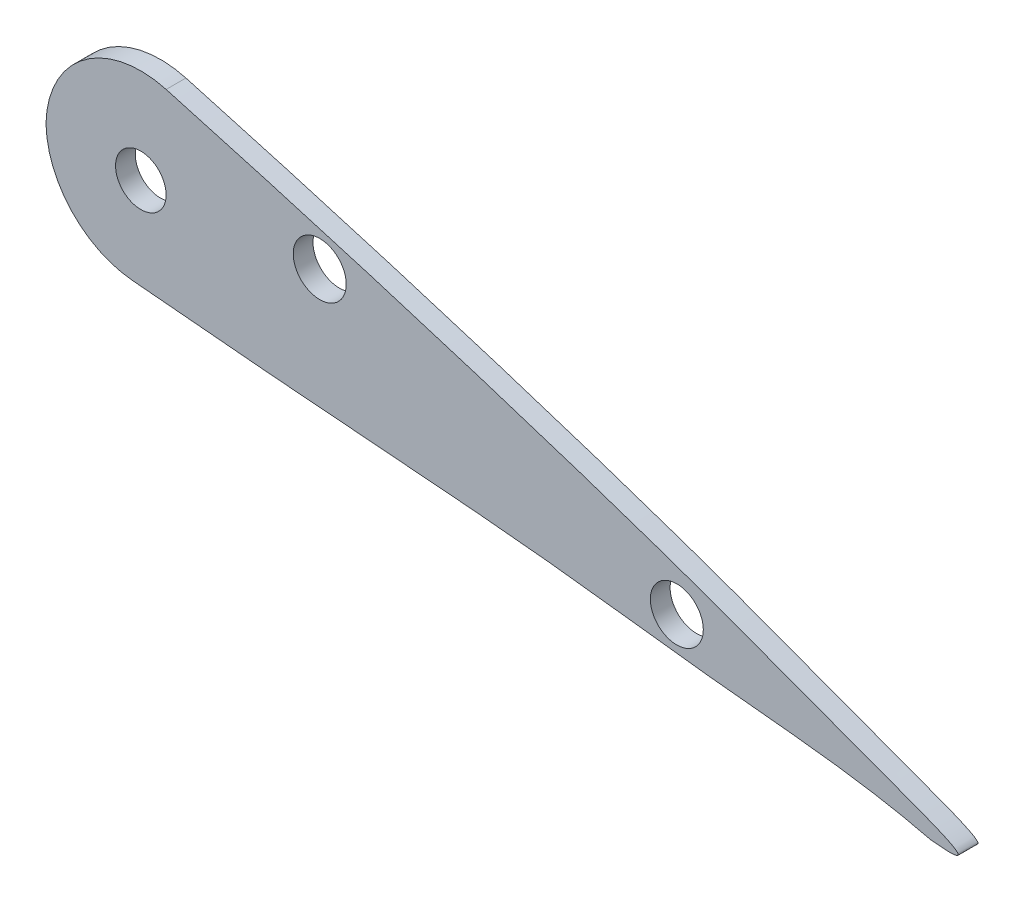
SolidWorks part; units mm, degrees
material "Balsa"
ref_plane "Front Plane" through (0, 0, 0) normal (0, 0, 1) x (1, 0, 0)
ref_plane "Top Plane" through (0, 0, 0) normal (0, 1, 0) x (1, 0, 0)
ref_plane "Right Plane" through (0, 0, 0) normal (1, 0, 0) x (0, 0, -1)
sketch "Sketch1" plane through (0, 0, 0) normal (0, 0, 1) x (1, 0, 0)
  spline S0 degree 3 poles (0.0006, 0.0001) (0.8106, 7.3592) (8.6491, 17.8566) (26.2867, 29.9752) (52.1111, 42.0692) (89.5976, 49.2908) (131.4008, 47.8848) (173.2567, 40.0411) (217.9611, 29.613) (256.9521, 19.5289) (290.3598, 8.711) (301.2732, 4.3828) (314.8169, -0.5162) (309.8463, 0.0001) knots 0 0 0 0 0.060864 0.113688 0.188609 0.312909 0.448482 0.557612 0.691544 0.852438 0.929756 0.976058 1 1 1 1
  spline S1 degree 3 poles (309.8463, 0.0001) (303.9568, 1.471) (293.9895, 2.094) (276.264, 4.5144) (260.8463, 5.4274) (235.8588, 7.8703) (205.1014, 8.8381) (157.7186, 9.0307) (110.4973, 6.1815) (66.5062, -0.5867) (36.4547, -6.0985) (15.3166, -6.1891) (1.2307, -6.9241) (0.0006, 0.0001) knots 0 0 0 0 0.057787 0.095275 0.171021 0.205339 0.335319 0.464904 0.658702 0.785512 0.893517 0.943092 1 1 1 1
extrude "Boss-Extrude1" add sketch "Sketch1" along normal blind 1.5875
sketch "Sketch2" plane through (0, 0, 1.5875) normal (0, 0, 1) x (1, 0, 0)
  circle A0 centre (20.32, 10.16) radius 6.35
  circle A1 centre (227.2963, 19.0501) radius 3.175
  dimension "D2" = 12.7
  dimension "D3" = 6.35
  dimension "D6" = 20.32
  dimension "D1" = 82.55
  dimension "D4" = 19.05
  dimension "D5" = 10.16
extrude "Cut-Extrude1" cut sketch "Sketch2" against normal through all
sketch "Sketch3" plane through (0, 0, 1.5875) normal (0, 0, 1) x (1, 0, 0)
  line L11 (-90.3395, -69.7561) -> (238.7263, -69.7561)
  line L12 (-90.3395, -69.7561) -> (-90.3395, 107.5465)
  line L13 (-90.3395, 107.5465) -> (238.7263, 107.5465)
  line L14 (238.7263, -69.7561) -> (238.7263, 107.5465)
  circle A1 centre (227.2963, 19.0501) radius 3.175 construction
  dimension "D1" = 11.43
extrude "Cut-Extrude2" cut sketch "Sketch3" against normal through all contours L14 L13 L12 L11
fillet "Fillet1" radius 7.62 2 edges at (238.7263, 7.3795, 0.7937) (238.7263, 24.1211, 0.7937)
sketch "Sketch4" plane through (0, 0, 1.5875) normal (0, 0, 1) x (1, 0, 0)
  circle A0 centre (246.3463, 14.163) radius 2.032
  dimension "D1" = 4.064
  dimension "D2" = 63.5
  dimension "D3" = 14.1628
extrude "Cut-Extrude3" cut sketch "Sketch4" against normal blind 2.54
sketch "Sketch5" plane through (0, 0, 1.5875) normal (0, 0, 1) x (1, 0, 0)
  circle A0 centre (260.7202, 15.1782) radius 2.127
  circle A1 centre (289.4099, 5.4937) radius 2.127
  point P4 (284.5248, 6.5939)
  point P5 (289.4099, 5.4937)
  dimension "D1" = 4.254
extrude "Cut-Extrude4" cut sketch "Sketch5" against normal blind 2.54
equation "\"D1@Sketch3\"=0.25+0.2"
